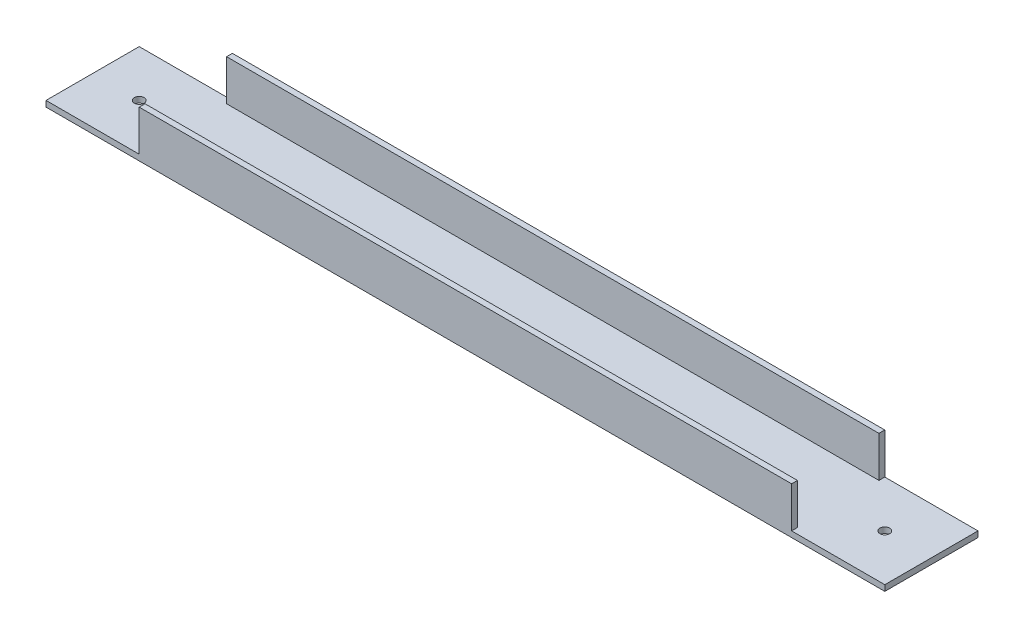
SolidWorks part; units mm, degrees
ref_plane "Front" through (0, 0, 0) normal (0, 0, 1) x (1, 0, 0)
ref_plane "Top" through (0, 0, 0) normal (0, 1, 0) x (1, 0, 0)
ref_plane "Right" through (0, 0, 0) normal (1, 0, 0) x (0, 0, -1)
sketch "Sketch1" plane through (0, 0, 0) normal (1, 0, 0) x (0, 0, -1)
  line L0 (3.175, 3.175) -> (3.175, 25.4)
  line L1 (0, 0) -> (50.8, 0)
  line L2 (0, 0) -> (0, 25.4)
  line L4 (50.8, 0) -> (50.8, 25.4)
  line L5 (3.175, 3.175) -> (47.625, 3.175)
  line L6 (47.625, 3.175) -> (47.625, 25.4)
  line L7 (0, 25.4) -> (3.175, 25.4)
  line L8 (50.8, 25.4) -> (47.625, 25.4)
  dimension "D1" = 25.4
  dimension "D2" = 50.8
  dimension "D3" = 3.175
extrude "Boss-Extrude1" add sketch "Sketch1" along normal blind 457.2
sketch "Sketch2" plane through (0, 25.4, 0) normal (0, 1, 0) x (1, 0, 0)
  line L0 (457.2, 50.8) -> (0, 50.8) construction
  line L1 (0, 0) -> (50.8, 0)
  line L2 (0, 0) -> (0, 50.8)
  line L3 (0, 50.8) -> (50.8, 50.8)
  line L4 (50.8, 0) -> (50.8, 50.8)
  line L5 (0, 0) -> (50.8, 50.8) construction
  line L6 (0, 50.8) -> (50.8, 0) construction
  line L8 (457.2, 0) -> (406.4, 0)
  line L9 (457.2, 0) -> (457.2, 50.8)
  line L10 (457.2, 50.8) -> (406.4, 50.8)
  line L11 (406.4, 0) -> (406.4, 50.8)
  line L12 (457.2, 0) -> (406.4, 50.8) construction
  line L13 (457.2, 50.8) -> (406.4, 0) construction
  point P4 (25.4, 25.4)
  point P12 (431.8, 25.4)
  dimension "D1" = 50.8
extrude "Cut-Extrude1" cut sketch "Sketch2" against normal up to surface (22.225 mm away) up to face at (228.6, 3.175, -25.4)
sketch "Sketch3" plane through (0, 0, 0) normal (0, -1, 0) x (1, 0, 0)
  line L0 (0, -25.4) -> (25.4, -25.4) construction
  line L1 (0, 0) -> (0, -50.8) construction
  line L2 (228.6, 0) -> (228.6, -50.8) construction
  line L3 (457.2, 0) -> (0, 0) construction
  line L4 (457.2, -50.8) -> (0, -50.8) construction
  circle A0 centre (25.4, -25.4) radius 2.667
  circle A1 centre (431.8, -25.4) radius 2.667
  dimension "D2" = 5.334
  dimension "D1" = 25.4
extrude "Cut-Extrude2" cut sketch "Sketch3" against normal up to next
